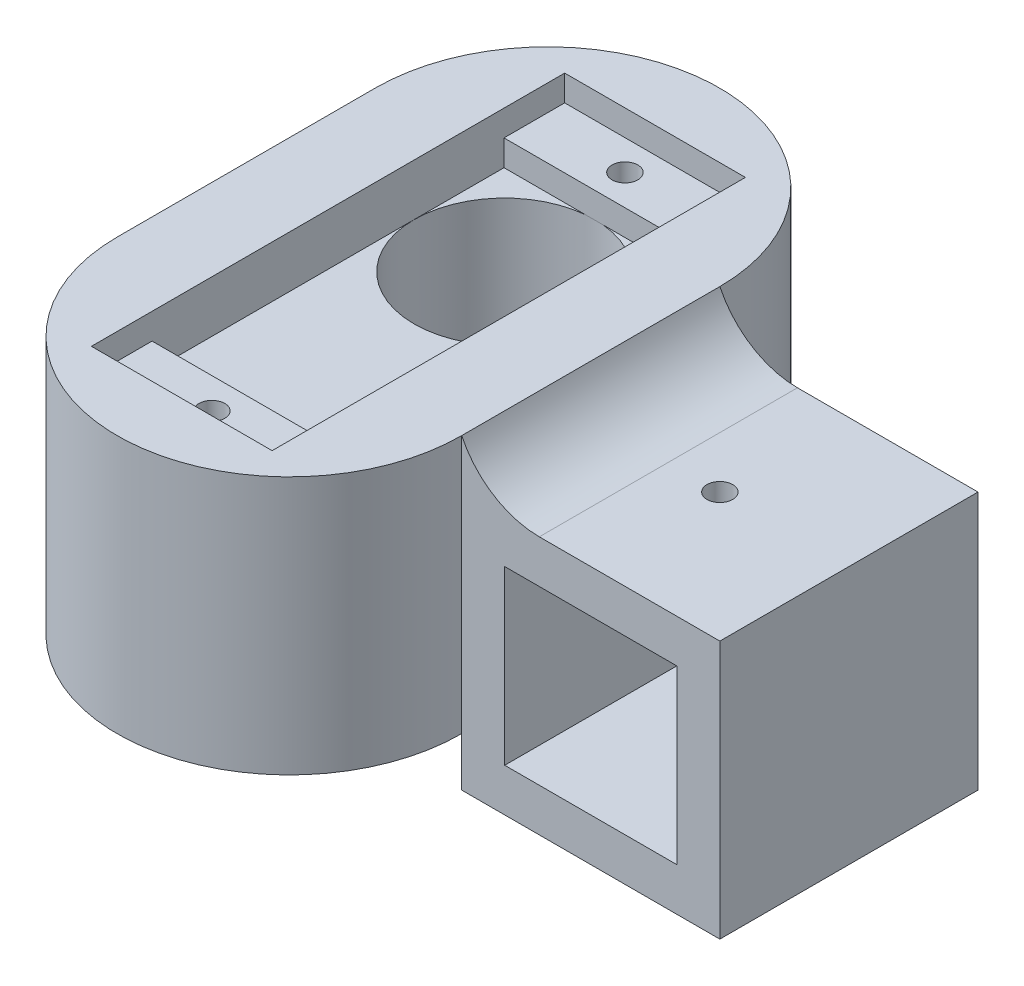
SolidWorks part; units mm, degrees
ref_plane "Front Plane" through (0, 0, 0) normal (0, 0, 1) x (1, 0, 0)
ref_plane "Top Plane" through (0, 0, 0) normal (0, 1, 0) x (1, 0, 0)
ref_plane "Right Plane" through (0, 0, 0) normal (1, 0, 0) x (0, 0, -1)
sketch "Sketch1" plane through (0, 0, 0) normal (0, 0, 1) x (1, 0, 0)
  line L15 (-10, 10) -> (10, 10)
  line L34 (-10, 10) -> (-10, -10)
  line L35 (-10, -10) -> (10, -10)
  line L50 (10, 10) -> (10, -10)
  line L51 (-10, 10) -> (10, -10) construction
  line L66 (-10, -10) -> (10, 10) construction
  line L73 (-15, 15) -> (15, 15)
  line L74 (-15, 15) -> (-15, -15)
  line L75 (-15, -15) -> (15, -15)
  line L76 (15, 15) -> (15, -15)
  point P1 (0, 0)
  dimension "D1" = 20
  dimension "D2" = 30
  dimension "D3" = 30
  dimension "D4" = 20
extrude "Boss-Extrude2" add sketch "Sketch1" along normal blind 30 contours L76 L73 L74 L75 L34 region at (0, 14.5757, 0)
ref_plane "Plane1" through (0, 20.68, 0) normal (0, 1, 0) x (1, 0, 0)
sketch "Sketch5" plane through (0, 20.68, 0) normal (0, 1, 0) x (1, 0, 0)
  line L4 (-35, -30.0309) -> (-35, -0.0309) construction
  line L5 (-15, -30.0309) -> (-15, -0.0309)
  line L6 (-55, -30.0309) -> (-55, -0.0309)
  arc A2 (-15, -30.0309) -> (-55, -30.0309) centre (-35, -30.0309) cw
  arc A3 (-55, -0.0309) -> (-15, -0.0309) centre (-35, -0.0309) cw
  point P12 (-35, -15.0309)
extrude "Boss-Extrude3" add sketch "Sketch5" against normal blind 30
sketch "Sketch6" plane through (0, 20.68, 0) normal (0, 1, 0) x (1, 0, 0)
  line L0 (-35, -50.0309) -> (-35, 19.9691) construction
  line L2 (-45.5, -42.5309) -> (-24.5, -42.5309)
  line L3 (-45.5, -42.5309) -> (-45.5, 12.4691)
  line L4 (-45.5, 12.4691) -> (-24.5, 12.4691)
  line L5 (-24.5, -42.5309) -> (-24.5, 12.4691)
  line L6 (-45.5, -42.5309) -> (-24.5, 12.4691) construction
  line L7 (-45.5, 12.4691) -> (-24.5, -42.5309) construction
  arc A0 (-55, -30.0309) -> (-15, -30.0309) centre (-35, -30.0309) ccw construction
  arc A1 (-15, -0.0309) -> (-55, -0.0309) centre (-35, -0.0309) ccw construction
  point P8 (-35, -15.0309)
  dimension "D1" = 21
  dimension "D2" = 55
extrude "Cut-Extrude1" cut sketch "Sketch6" against normal blind 3
sketch "Sketch7" plane through (0, 17.68, 0) normal (0, 1, 0) x (1, 0, 0)
  line L0 (-35, -42.5309) -> (-35, 12.4691) construction
  line L1 (-45.5, -42.5309) -> (-24.5, -42.5309) construction
  line L2 (-24.5, 12.4691) -> (-45.5, 12.4691) construction
  circle A0 centre (-35, -39.0309) radius 1.5
  circle A1 centre (-35, 8.9691) radius 1.5
  dimension "D1" = 3
  dimension "D2" = 3
  dimension "D3" = 48
  dimension "D4" = 3.5
extrude "Cut-Extrude2" cut sketch "Sketch7" against normal blind 5
sketch "Sketch8" plane through (0, 17.68, 0) normal (0, 1, 0) x (1, 0, 0)
  line L0 (-35, -42.5309) -> (-35, 12.4691) construction
  line L1 (-45.5, -42.5309) -> (-24.5, -42.5309) construction
  line L2 (-24.5, 12.4691) -> (-45.5, 12.4691) construction
  line L4 (-45.5, -35.4809) -> (-24.5, -35.4809)
  line L5 (-45.5, -35.4809) -> (-45.5, 5.4191)
  line L6 (-45.5, 5.4191) -> (-24.5, 5.4191)
  line L7 (-24.5, -35.4809) -> (-24.5, 5.4191)
  line L8 (-45.5, -35.4809) -> (-24.5, 5.4191) construction
  line L9 (-45.5, 5.4191) -> (-24.5, -35.4809) construction
  point P6 (-35, -15.0309)
  dimension "D1" = 21
  dimension "D2" = 40.9
extrude "Cut-Extrude3" cut sketch "Sketch8" against normal blind 3
sketch "Sketch9" plane through (0, 14.68, 0) normal (0, 1, 0) x (1, 0, 0)
  line L0 (-35, -35.4809) -> (-35, 5.4191) construction
  line L1 (-45.5, -35.4809) -> (-24.5, -35.4809) construction
  line L2 (-24.5, 5.4191) -> (-45.5, 5.4191) construction
  circle A0 centre (-35, -5.0309) radius 10.5
  point P8 (-35, -15.0309)
  dimension "D2" = 21
  dimension "D1" = 10
extrude "Cut-Extrude4" cut sketch "Sketch9" against normal through all
sketch "Sketch10" plane through (0, -9.32, 0) normal (0, -1, 0) x (1, 0, 0)
  circle A0 centre (-35, 5.0309) radius 10.5
  circle A1 centre (-35, 5.0309) radius 10.5 construction
  circle A2 centre (-35, 5.0309) radius 4
  dimension "D1" = 8
extrude "Boss-Extrude4" add sketch "Sketch10" against normal blind 10
fillet "Fillet1" radius 10 1 edges at (-15, 15, 15.0155)
sketch "Sketch11" plane through (0, 15, 0) normal (0, 1, 0) x (1, 0, 0)
  line L0 (-5.9813, 0) -> (15, 0) construction
  line L1 (15, -30) -> (15, 0) construction
  circle A0 centre (0, -15) radius 1.5
  dimension "D1" = 3
  dimension "D2" = 15
  dimension "D3" = 15
extrude "Cut-Extrude5" cut sketch "Sketch11" against normal through all
